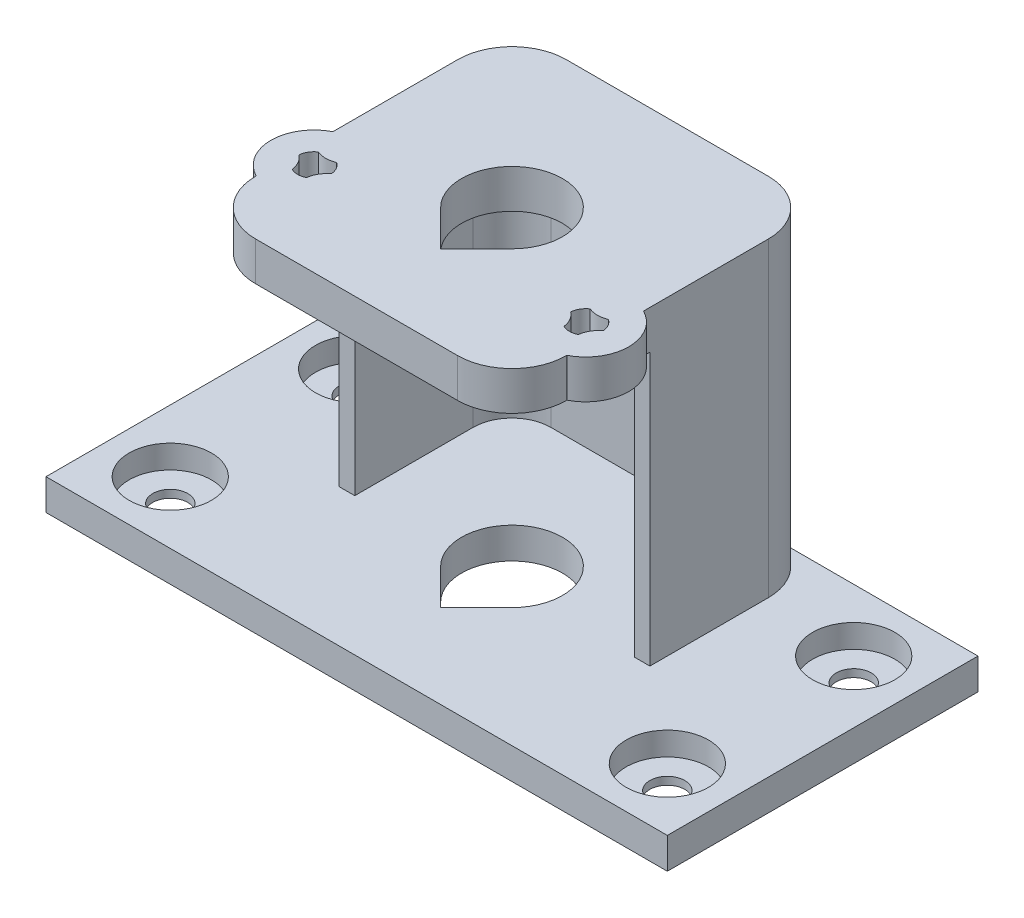
SolidWorks part; units mm, degrees
note: The reader was unsure of these and kept them because the rebuilt part matched: shared geometry of "Esquisse1<3>".
ref_plane "Plan de face" through (0, 0, 0) normal (0, 0, 1) x (1, 0, 0)
ref_plane "Plan de dessus" through (0, 0, 0) normal (0, 1, 0) x (1, 0, 0)
ref_plane "Plan de droite" through (0, 0, 0) normal (1, 0, 0) x (0, 0, -1)
sketch "Esquisse1" plane through (0, 0, 0) normal (0, 1, 0) x (1, 0, 0)
  line L0 (0, 0) -> (0, -8) construction
  line L1 (-17.5, -8) -> (17.5, -8) construction
  line L2 (-17.5, -3.5) -> (-17.5, -8) construction
  line L3 (-20, 20) -> (20, 20)
  line L4 (-20, 20) -> (-20, -20)
  line L5 (-20, -20) -> (20, -20)
  line L6 (20, 20) -> (20, -20)
  line L7 (-20, 20) -> (20, -20) construction
  line L8 (-20, -20) -> (20, 20) construction
  line L9 (-17.5, -8) -> (-17.5, -10.25) construction
  line L10 (4.5962, -4.5962) -> (0, -9.1924)
  line L11 (0, -9.1924) -> (-4.5962, -4.5962)
  line L12 (0, -8) -> (0, -9.1924) construction
  circle A0 centre (0, 0) radius 6.5
  arc A1 (-20, -3.0674) -> (-20, -12.9326) centre (-17.5, -8) ccw
  arc A2 (20, -3.0674) -> (20, -12.9326) centre (17.5, -8) cw
  circle A3 centre (-17.5, -8) radius 2.1
  arc A4 (-18.6758, -6.26) -> (-16.3242, -6.26) centre (-17.5, -3.5) ccw
  arc A5 (-15.4052, -7.8518) -> (-16.581, -9.8882) centre (-13.6029, -10.25) ccw
  arc A6 (-18.419, -9.8882) -> (-19.5948, -7.8518) centre (-21.3971, -10.25) ccw
  circle A7 centre (17.5, -8) radius 2.1
  arc A8 (15.4052, -7.8518) -> (16.581, -9.8882) centre (13.6029, -10.25) cw
  arc A9 (18.419, -9.8882) -> (19.5948, -7.8518) centre (21.3971, -10.25) cw
  arc A10 (18.6758, -6.26) -> (16.3242, -6.26) centre (17.5, -3.5) cw
  point P6 (0, -8)
  point P7 (0, 0)
  point P20 (-17.5, -5.75)
  point P23 (-17.5, -9.65)
  point P27 (-17.5, -6.5)
  dimension "D1" = 13
  dimension "D4" = 40
  dimension "D5" = 5.53
  dimension "D6" = 4.2
  dimension "D7" = 0.6
  dimension "D2" = 8
  dimension "D3" = 35
  dimension "D8" = 0.75
  dimension "D9" = 3
extrude "Boss.-Extru.1" add sketch "Esquisse1" against normal blind 5 contours L4 A1 | L6 L3 L4 L5 A0 A3 A7 | A3 A5 | A3 A6 | A3 A4 | A8 A7 | A10 A7 | A9 A7 | A2 L6
sketch "Esquisse7" plane through (0, -5, 0) normal (0, -1, 0) x (1, 0, 0)
  line L0 (0, 0) -> (0, 8) construction
  line L1 (-20, -20) -> (-18, -20)
  line L2 (-20, -20) -> (-20, 2.2434)
  line L3 (-20, 2.2434) -> (-18, 2.2434)
  line L4 (-18, -20) -> (-18, 2.2434)
  line L5 (20, 2.2434) -> (18, 2.2434)
  line L6 (18, -20) -> (18, 2.2434)
  line L7 (20, -20) -> (18, -20)
  line L8 (20, -20) -> (20, 2.2434)
  line L9 (-18, -18) -> (18, -18)
  line L10 (0, -18) -> (0, -20) construction
  line L11 (-20, -20) -> (20, -20) construction
  line M8 (-20, 3.0674) -> (-20, -20)
  line M9 (-20, -20) -> (20, -20)
  line M10 (20, -20) -> (20, 3.0674)
  dimension "D1" = 2
extrude "Boss.-Extru.2" add sketch "Esquisse7" along normal blind 35 contours L4 L3 M9 M8 | L9 L4 L6 M9 | L6 L5 M9 M10
sketch "Esquisse9" plane through (0, -40, 0) normal (0, -1, 0) x (1, 0, 0)
  line L0 (0, 20) -> (0, -20) construction
  line L1 (-20, -20) -> (20, -20)
  line L2 (-20, -20) -> (-20, 20)
  line L3 (-20, 20) -> (20, 20)
  line L4 (20, -20) -> (20, 20)
  line L5 (-20, 20) -> (-40, 20)
  line L6 (-20, 20) -> (-20, -20)
  line L7 (-20, -20) -> (-40, -20)
  line L8 (-40, 20) -> (-40, -20)
  line L9 (20, -20) -> (40, -20)
  line L10 (40, 20) -> (40, -20)
  line L11 (20, 20) -> (40, 20)
  line L12 (20, 20) -> (20, -20)
  line L13 (-20, -20) -> (20, -20) construction
  line M5 (-20, -20) -> (20, -20)
  line M6 (20, -20) -> (20, 2.2434)
  line M7 (20, 2.2434) -> (18, 2.2434)
  line M8 (18, 2.2434) -> (18, -18)
  line M9 (18, -18) -> (-18, -18)
  line M10 (-18, -18) -> (-18, 2.2434)
  line M11 (-18, 2.2434) -> (-20, 2.2434)
  line M12 (-20, 2.2434) -> (-20, -20)
  dimension "D1" = 20
extrude "Boss.-Extru.4" add sketch "Esquisse9" along normal blind 4 contours L5 L8 L7 L2 M12 | L11 L4 L9 L10 M6 | L0 L3 L2 M11 M10 M9 | L0 M9 M10 M11 M12 M5 | L0 L1 M9 M6 M7 M8 | L3 L0 L4 M9 M8 M7
extrude "Enlèv. mat.-Extru.2" cut sketch "Esquisse1<3>" against normal through all contours A0 | A0 L11 L10
sketch "Esquisse1<3>" plane through (0, 0, 0) normal (0, 1, 0) x (1, 0, 0) same geometry as "Esquisse1"
hole_wizard "Chambrage pour vis à tête hexagonale M41" positions "Esquisse14" profile "Esquisse15" counterbore size "M4" standard "Ansi Metric"
sketch "Esquisse14" plane through (0, -40, 0) normal (0, 1, 0) x (1, 0, 0)
  line L0 (0, 20) -> (0, -20) construction
  line L1 (-20, 20) -> (20, 20) construction
  line L2 (-20, -20) -> (20, -20) construction
  line L5 (-40, -20) -> (40, -20)
  line L6 (-40, -20) -> (-40, 20)
  line L7 (-40, 20) -> (40, 20)
  line L8 (40, -20) -> (40, 20)
  line L9 (0, 0) -> (5.9812, 0) construction
  point P72 (-32, 12)
  point P74 (32, 12)
  point P79 (32, -12)
  point P80 (-32, -12)
  dimension "D1" = 8
  dimension "D2" = 8
sketch "Esquisse15" plane through (-32, -40, 12) normal (1, 0, 0) x (0, 0, 1)
  line L0 (0, 0) -> (0, 5.3519)
  line L1 (0, 5.3519) -> (2.25, 4)
  line L2 (2.25, 4) -> (2.25, 3)
  line L3 (2.25, 3) -> (5.295, 3)
  line L4 (5.295, 3) -> (5.295, 0)
  line L5 (5.295, 0) -> (0, 0)
  line L10 (0, 5.3519) -> (-2.25, 4) construction
  line L11 (0, -6.35) -> (0, 107.95) construction
  dimension "Diamètre du perçage" = 4.5
  dimension "Profondeur du perçage" = 4
  dimension "Diamètre du chambrage" = 10.59
  dimension "Profondeur du chambrage" = 3
  dimension "Angle de pointe" = 118
fillet "Congé1" radius 5 2 edges at (18, -22.5, -18) (-18, -22.5, -18)
fillet "Congé2" radius 7 4 edges at (-20, -20, -20) (20, -20, -20) (20, -2.5, 20) (-20, -2.5, 20)
